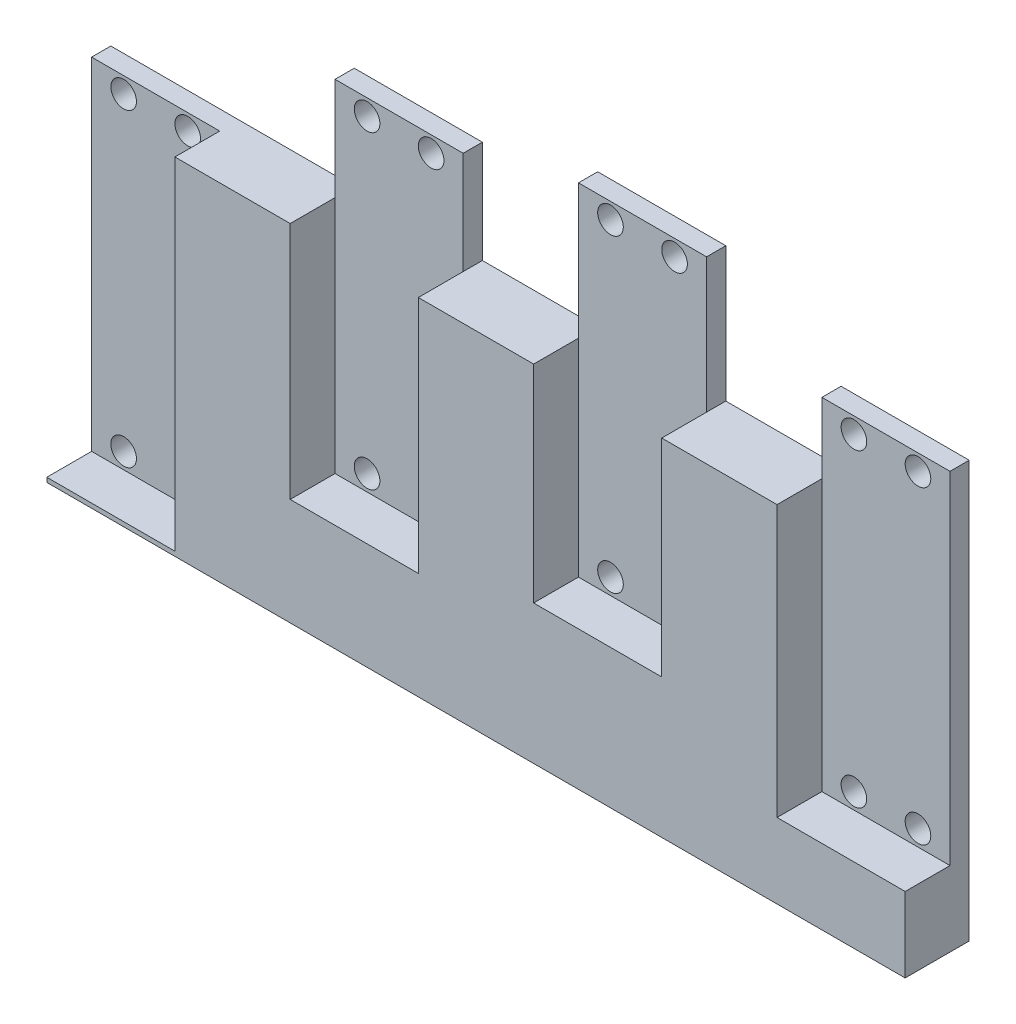
SolidWorks part; units mm, degrees
ref_plane "Front Plane" through (0, 0, 0) normal (0, 0, 1) x (1, 0, 0)
ref_plane "Top Plane" through (0, 0, 0) normal (0, 1, 0) x (1, 0, 0)
ref_plane "Right Plane" through (0, 0, 0) normal (1, 0, 0) x (0, 0, -1)
sketch "Sketch1" plane through (0, 0, 0) normal (0, 0, 1) x (1, 0, 0)
  line L0 (-60, 25) -> (30, 25)
  line L1 (-60, -29) -> (74, -29)
  line L2 (-60, -29) -> (-60, 25)
  line L3 (-60, 25) -> (74, 25)
  line L4 (74, -29) -> (74, 25)
  line L5 (-60, -29) -> (74, 25) construction
  line L6 (-60, 25) -> (74, -29) construction
  line L8 (-60, 25) -> (-31, 25)
  line L9 (-31, 25) -> (7, 25)
  line L10 (7, 25) -> (45, 25)
  line L11 (45, 25) -> (74, 25)
  line L12 (-31, 25) -> (7, 25)
  line L13 (-31, 25) -> (-31, 41)
  line L14 (7, 25) -> (7, 41)
  line L15 (-31, 41) -> (7, 41)
  line L16 (7, 25) -> (45, 25)
  line L17 (7, 25) -> (7, 46)
  line L18 (45, 25) -> (45, 46)
  line L19 (7, 46) -> (45, 46)
  line L20 (45, 25) -> (74, 25)
  line L21 (45, 25) -> (45, 36)
  line L22 (74, 25) -> (74, 36)
  line L23 (45, 36) -> (74, 36)
  point P0 (0, 0)
  dimension "D1" = 134
  dimension "D2" = 54
  dimension "D3" = 29
  dimension "D4" = 38
  dimension "D5" = 38
  dimension "D6" = 29
  dimension "D7" = 16
  dimension "D8" = 21
  dimension "D9" = 11
extrude "Boss-Extrude1" add sketch "Sketch1" along normal blind 10 contours L1 L4 L3 L0 L2 | L23 L18 L3 L22 | L19 L17 L14 L0 L3 L18 | L15 L13 L3 L14 region at (7, -2, 0) region at (-12, 33, 0) region at (26, 35.5, 0) region at (59.5, 30.5, 0)
sketch "Sketch3" plane through (0, 0, 10) normal (0, 0, 1) x (1, 0, 0)
  line L0 (-60, 25) -> (-40, 25)
  line L1 (-60, 25) -> (-40, 25)
  line L2 (-60, 25) -> (-60, -28.3)
  line L3 (-40, 25) -> (-40, -28.3)
  line L4 (-60, -28.3) -> (-40, -28.3)
  line L6 (-31, 41) -> (7, 41) construction
  line L7 (-22, 41) -> (-22, -12.3)
  line L8 (-22, 41) -> (-22, -12.3)
  line L9 (-22, 41) -> (-2, 41)
  line L10 (-22, -12.3) -> (-2, -12.3)
  line L11 (-2, 41) -> (-2, -12.3)
  line L13 (-2, -12.3) -> (-2, 38.1827)
  line L14 (16, 46) -> (16, -7.3)
  line L15 (16, 46) -> (16, -7.3)
  line L16 (16, 46) -> (36, 46)
  line L17 (16, -7.3) -> (36, -7.3)
  line L18 (36, 46) -> (36, -7.3)
  line L20 (7, 46) -> (45, 46) construction
  line L21 (54, 36) -> (54, -17.3)
  line L22 (54, 36) -> (54, -17.3)
  line L23 (54, 36) -> (74, 36)
  line L24 (54, -17.3) -> (74, -17.3)
  line L25 (74, 36) -> (74, -17.3)
  line L26 (-60, 25) -> (-60, 22.5)
  line L27 (-60, 25) -> (-55, 25)
  line L28 (-60, 22.5) -> (-55, 22.5)
  line L29 (-55, 25) -> (-55, 22.5)
  line L30 (-50, 25) -> (-50, -28.3)
  line L31 (-60, -1.65) -> (-40, -1.65)
  line L32 (-22, 14.35) -> (-2, 14.35)
  line L33 (-12, 41) -> (-12, -12.3)
  line L34 (26, -7.3) -> (26, 46)
  line L35 (16, 19.35) -> (36, 19.35)
  line L36 (64, 36) -> (64, -17.3)
  line L37 (54, 9.35) -> (74, 9.35)
  line L38 (-22, 41) -> (-22, 38.5)
  line L39 (-22, 41) -> (-17, 41)
  line L40 (-22, 38.5) -> (-17, 38.5)
  line L41 (-17, 41) -> (-17, 38.5)
  line L42 (16, 46) -> (16, 43.5)
  line L43 (16, 46) -> (21, 46)
  line L44 (16, 43.5) -> (21, 43.5)
  line L45 (21, 46) -> (21, 43.5)
  line L46 (54, 36) -> (54, 33.5)
  line L47 (54, 36) -> (59, 36)
  line L48 (54, 33.5) -> (59, 33.5)
  line L49 (59, 36) -> (59, 33.5)
  circle A0 centre (-55, 22.5) radius 2
  circle A1 centre (-45, 22.5) radius 2
  circle A2 centre (-45, -25.8) radius 2
  circle A3 centre (-55, -25.8) radius 2
  circle A4 centre (-17, 38.5) radius 2
  circle A5 centre (-7, 38.5) radius 2
  circle A6 centre (-7, -9.8) radius 2
  circle A7 centre (-17, -9.8) radius 2
  circle A8 centre (21, 43.5) radius 2
  circle A9 centre (31, 43.5) radius 2
  circle A10 centre (31, -4.8) radius 2
  circle A11 centre (21, -4.8) radius 2
  circle A12 centre (59, 33.5) radius 2
  circle A13 centre (69, 33.5) radius 2
  circle A14 centre (69, -14.8) radius 2
  circle A15 centre (59, -14.8) radius 2
  point P8 (-12, 41)
  point P9 (0, 0)
  point P83 (26, 46)
  line M9 (-60, 25) -> (-60, -29)
  line M140 (7, 41) -> (-31, 41)
  line M142 (-31, 25) -> (-60, 25)
  line M144 (74, 36) -> (45, 36)
  line M152 (45, 46) -> (7, 46)
  dimension "D16" = 4
  dimension "D19" = 4
  dimension "D22" = 4
  dimension "D25" = 4
  dimension "D1" = 20
  dimension "D2" = 53.3
  dimension "D4" = 53.3
  dimension "D5" = 20
  dimension "D9" = 53.3
  dimension "D10" = 20
  dimension "D12" = 53.3
  dimension "D13" = 20
  dimension "D14" = 2.5
  dimension "D15" = 5
  dimension "D17" = 2.5
  dimension "D18" = 5
  dimension "D20" = 2.5
  dimension "D21" = 5
  dimension "D23" = 2.5
  dimension "D24" = 5
extrude "Cut-Extrude1" cut sketch "Sketch3" against normal up to next contours L28 A0 L29 | L29 A0 L28 | A1 | A2 | A3 | L40 A4 L41 | L41 A4 L40 | A5 | A6 | A7 | L44 A8 L45 | L45 A8 L44 | A9 | A10 | A11 | A15 | A14 | A13 | L48 A12 L49 | L49 A12 L48 region at (-54.7171, 22.2171, 10) region at (-55.8488, 23.3488, 10) region at (-17.8488, 39.3488, 10) region at (-16.7171, 38.2171, 10) region at (20.1512, 44.3488, 10) region at (21.2829, 43.2171, 10) region at (58.1512, 34.3488, 10) region at (59.2829, 33.2171, 10) region at (-45, 22.5, 10) region at (-45, -25.8, 10) region at (-55, -25.8, 10) region at (-7, 38.5, 10) region at (-7, -9.8, 10) region at (-17, -9.8, 10) region at (31, 43.5, 10) region at (31, -4.8, 10) region at (21, -4.8, 10) region at (69, 33.5, 10) region at (69, -14.8, 10) region at (59, -14.8, 10)
extrude "Cut-Extrude2" cut sketch "Sketch3<11>" against normal blind 7 contours A0 L28 L2 L31 L30 L1 L29 | A0 L29 L1 L28 M9 | L30 L31 L3 A1 M142 | L31 L30 L4 L3 A2 | L31 L4 L30 A3 M9 | L33 L32 L8 L10 A7 | L32 L33 L10 L13 A6 | A4 L40 L8 L32 L33 L9 L41 | L33 L32 L11 A5 M140 | A4 L41 L7 L40 M140 | A8 L44 L15 L35 L34 L16 L45 | L34 L35 L18 A9 M152 | A8 L45 L14 L44 M152 | L35 L15 L17 L34 A11 | L35 L34 L17 L18 A10 | A12 L48 L22 L37 L36 L23 L49 | L36 L37 L25 A13 M144 | A12 L49 L21 L48 M144 | L37 L22 L24 L36 A15 | L37 L36 L24 L25 A14 region at (-58.0543, 23.8847, 10) region at (-54.8831, 10.6516, 10) region at (-45, 11.1393, 10) region at (-55, -14.4393, 10) region at (-45, -14.4393, 10) region at (-20.0543, 39.8847, 10) region at (-16.8831, 26.6516, 10) region at (-17, 1.5607, 10) region at (-7, 27.1393, 10) region at (-7, 1.5607, 10) region at (17.9457, 44.8847, 10) region at (21.1169, 31.6516, 10) region at (21, 6.5607, 10) region at (31, 32.1393, 10) region at (31, 6.5607, 10) region at (55.9457, 34.8847, 10) region at (59.1169, 21.6516, 10) region at (59, -3.4393, 10) region at (69, 22.1393, 10) region at (69, -3.4393, 10)
sketch "Sketch3<11>" plane through (0, 0, 10) normal (0, 0, 1) x (1, 0, 0) same geometry as "Sketch3"
sketch "Sketch4" plane through (0, 0, 10) normal (0, 0, 1) x (1, 0, 0)
  line L0 (-31, 25) -> (-22, 25)
  line L1 (-31, 25) -> (-31, 41.0034)
  line L2 (-22, 25) -> (-22, 41.0034)
  line L3 (-31, 41.0034) -> (-22, 41.0034)
  line L4 (-22, 41) -> (-22, -12.3) construction
  line L6 (-2, 25) -> (16, 25)
  line L7 (-2, 25) -> (-2, 46)
  line L8 (16, 25) -> (16, 46)
  line L9 (-2, 46) -> (16, 46)
  line L10 (-2, 41) -> (-2, -12.3) construction
  line L11 (16, 46) -> (16, -7.3) construction
  line L13 (36, 25) -> (54, 25)
  line L14 (36, 25) -> (36, 46.2434)
  line L15 (54, 25) -> (54, 46.2434)
  line L16 (36, 46.2434) -> (54, 46.2434)
  line L19 (36, 46) -> (36, -7.3) construction
  line L20 (54, 36) -> (54, -17.3) construction
  line L21 (36, 46) -> (16, 46) construction
  point P25 (16, 46)
extrude "Cut-Extrude3" cut sketch "Sketch4" against normal up to next
equation "\"D8@Sketch1\"=\"Middle Height\""
equation "\"Servo Width\"= 20"
equation "\"Servo Height\"= 40"
equation "\"Ring Height\"= 16"
equation "\"Middle Height\"= 21"
equation "\"Pointer Height\"= 11"
equation "\"Finger Gap\"= 18"
equation "\"D1@Sketch1\"=(\"Servo Width\"*4)+(\"Finger Gap\"*3)"
equation "\"D3@Sketch1\"=\"Servo Width\"+(\"Finger Gap\"/2)"
equation "\"D4@Sketch1\"=\"Servo Width\"+\"Finger Gap\""
equation "\"D5@Sketch1\"=\"Servo Width\"+\"Finger Gap\""
equation "\"D7@Sketch1\"=\"Ring Height\""
equation "\"D9@Sketch1\"=\"Pointer Height\""
equation "\"Servo Total Height\"= 53.3"
equation "\"D2@Sketch3\"=\"Servo Total Height\""
equation "\"D4@Sketch3\"=\"Servo Total Height\""
equation "\"D9@Sketch3\"=\"Servo Total Height\""
equation "\"D12@Sketch3\"=\"Servo Total Height\""
equation "\"Servo Screw Height\"= 2.5"
equation "\"Servo Screw Width\"= 5"
equation "\"Servo Screw Diameter\"= 4"
equation "\"D1@Sketch3\"=\"Servo Width\""
equation "\"D5@Sketch3\"=\"Servo Width\""
equation "\"D10@Sketch3\"=\"Servo Width\""
equation "\"D13@Sketch3\"=\"Servo Width\""
equation "\"D14@Sketch3\"=\"Servo Screw Height\""
equation "\"D15@Sketch3\"=\"Servo Screw Width\""
equation "\"D16@Sketch3\"=\"Servo Screw Diameter\""
equation "\"D17@Sketch3\"=\"Servo Screw Height\""
equation "\"D18@Sketch3\"=\"Servo Screw Width\""
equation "\"D19@Sketch3\"=\"Servo Screw Diameter\""
equation "\"D20@Sketch3\"=\"Servo Screw Height\""
equation "\"D21@Sketch3\"=\"Servo Screw Width\""
equation "\"D22@Sketch3\"=\"Servo Screw Diameter\""
equation "\"D23@Sketch3\"=\"Servo Screw Height\""
equation "\"D24@Sketch3\"=\"Servo Screw Width\""
equation "\"D25@Sketch3\"=\"Servo Screw Diameter\""
